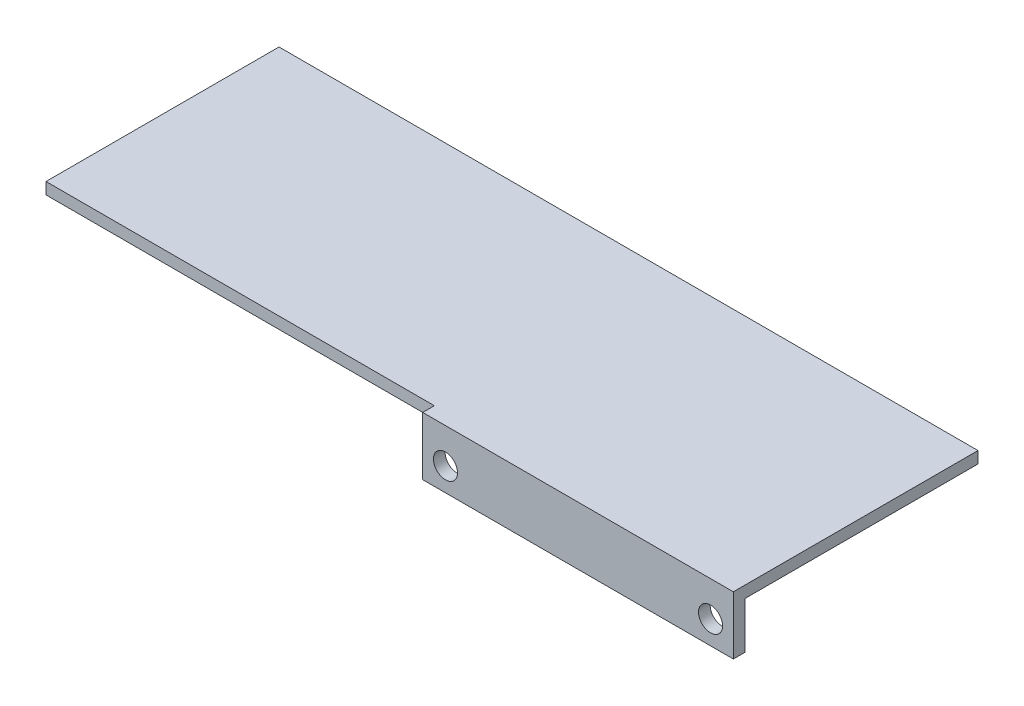
SolidWorks part; units mm, degrees
material "PTFE(普通)"
ref_plane "前视基准面" through (0, 0, 0) normal (0, 0, 1) x (1, 0, 0)
ref_plane "上视基准面" through (0, 0, 0) normal (0, 1, 0) x (1, 0, 0)
ref_plane "右视基准面" through (0, 0, 0) normal (1, 0, 0) x (0, 0, -1)
other "Configuration Table"
sketch "草图1" plane through (0, 0, 0) normal (0, 0, 1) x (1, 0, 0)
  line L1 (20, -3) -> (-20, -3)
  line L2 (20, -3) -> (20, 3)
  line L3 (20, 3) -> (-20, 3)
  line L4 (-20, -3) -> (-20, 3)
  line L5 (20, -3) -> (-20, 3) construction
  line L6 (20, 3) -> (-20, -3) construction
  circle A0 centre (-17.066, 0) radius 1.55
  circle A1 centre (17.066, 0) radius 1.55
  point P0 (0, 0)
  point P6 (-17.066, 0)
  point P7 (17.066, 0)
  dimension "D3" = 3.1
  dimension "D4" = 3.1
  dimension "D1" = 17.066
  dimension "D2" = 17.066
  dimension "D5" = 20
  dimension "D6" = 3
extrude "凸台-拉伸1" add sketch "草图1" along normal blind 1.5
sketch "草图2" plane through (0, 3, 0) normal (0, 1, 0) x (1, 0, 0)
  line L1 (-20, 0) -> (20, 0)
  line L2 (-20, 0) -> (-20, -1.5)
  line L3 (-20, -1.5) -> (20, -1.5)
  line L4 (20, 0) -> (20, -1.5)
extrude "凸台-拉伸2" add sketch "草图2" along normal blind 1.5
sketch "草图3" plane through (0, 0, 1.5) normal (0, 0, 1) x (1, 0, 0)
  line L0 (20, -3) -> (20, 4.5) construction
  line L1 (-20, 4.5) -> (20, 4.5)
  line L2 (-20, 4.5) -> (-20, 3)
  line L3 (-20, 3) -> (20, 3)
  line L4 (20, 4.5) -> (20, 3)
  dimension "D1" = 1.5
sketch "草图4" plane through (0, 0, 0) normal (0, 0, -1) x (-1, 0, 0)
  line L1 (-20, 4.5) -> (20, 4.5)
  line L2 (-20, 4.5) -> (-20, 3)
  line L3 (-20, 3) -> (20, 3)
  line L4 (20, 4.5) -> (20, 3)
extrude "凸台-拉伸3" add sketch "草图4" along normal blind 30
sketch "草图6" plane through (-20, 0, 0) normal (-1, 0, 0) x (0, 0, 1)
  line L1 (-30, 4.5) -> (0, 4.5)
  line L2 (-30, 4.5) -> (-30, 3)
  line L3 (-30, 3) -> (0, 3)
  line L4 (0, 4.5) -> (0, 3)
extrude "凸台-拉伸4" add sketch "草图6" along normal blind 50
